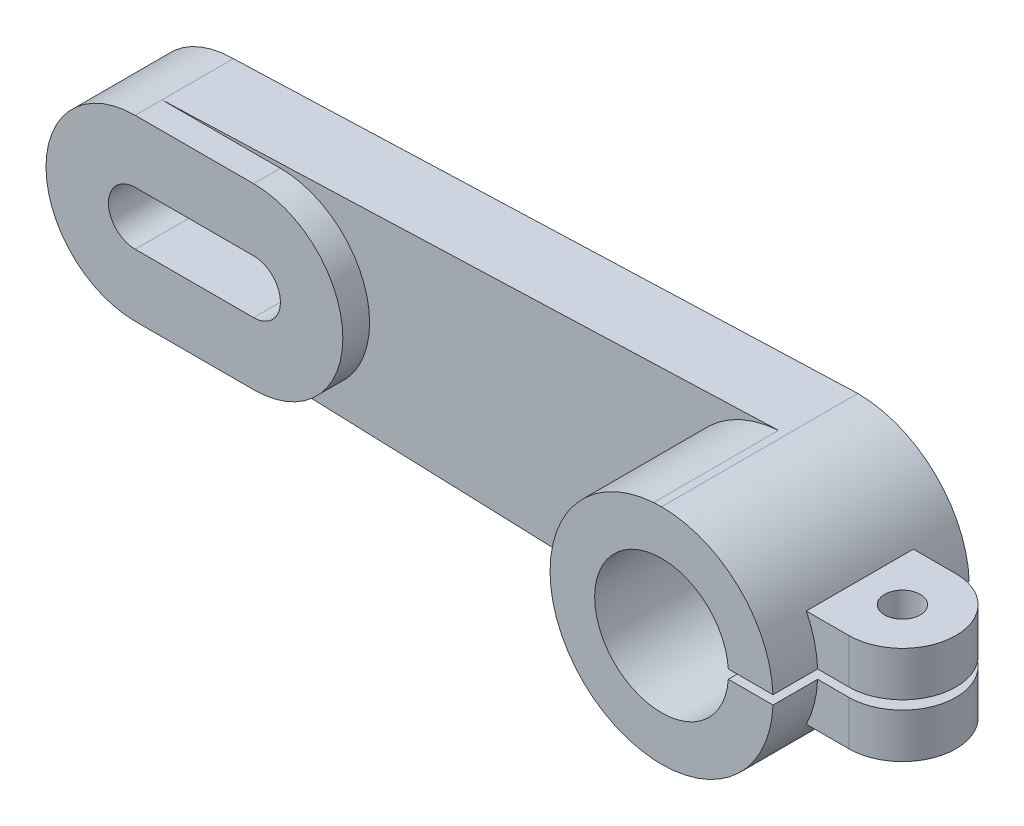
SolidWorks part; units mm, degrees
ref_plane "Přední rovina" through (0, 0, 0) normal (0, 0, 1) x (1, 0, 0)
ref_plane "Horní rovina" through (0, 0, 0) normal (0, 1, 0) x (1, 0, 0)
ref_plane "Pravá rovina" through (0, 0, 0) normal (1, 0, 0) x (0, 0, -1)
sketch "Skica2" plane through (0, 0, 0) normal (0, 0, 1) x (1, 0, 0)
  line L0 (0, 0) -> (140, 0) construction
  line L1 (0, 0) -> (26.5473, 0) construction
  line L2 (0, 6) -> (26.5473, 6)
  line L3 (0, -6) -> (26.5473, -6)
  line L4 (0, 0) -> (26.5473, 0) construction
  line L5 (0, 20) -> (26.5473, 20)
  line L6 (0, -20) -> (26.5473, -20)
  line L7 (0, 20) -> (140, 25)
  line L8 (0, -20) -> (140, -25)
  arc A0 (0, 6) -> (0, -6) centre (0, 0) ccw
  arc A1 (26.5473, -6) -> (26.5473, 6) centre (26.5473, 0) ccw
  arc A2 (0, 20) -> (0, -20) centre (0, 0) ccw
  arc A3 (26.5473, -20) -> (26.5473, 20) centre (26.5473, 0) ccw
  circle A4 centre (140, 0) radius 15
  circle A5 centre (140, 0) radius 25
  point P3 (13.2737, 0)
  point P9 (13.2737, 0)
  point P20 (0, 20)
  point P21 (140, 25)
  point P22 (0, 0)
  point P25 (0, 0)
  point P26 (0, 0)
  point P27 (0, 0)
  point P28 (140, -25)
  dimension "D3" = 50
  dimension "D4" = 30
  dimension "D1" = 6
  dimension "D2" = 20
  dimension "D5" = 140
extrude "Přidat vysunutím1" add sketch "Skica2" along normal blind 16 contours L6 A3 L5 A2 A1 L3 A0 L2 | A5 L7 L5 A3 L6 L8 | L7 A5 L8 A4 region at (81.0903, 0, 0) region at (13.2737, 19.2236, 0) region at (139.1335, 24.2615, 0)
extrude "Přidat vysunutím2" add sketch "Skica2<3>" along normal blind 22 contours L6 A3 L5 A2 A1 L3 A0 L2 region at (13.2737, 19.2236, 0)
sketch "Skica2<3>" plane through (0, 0, 0) normal (0, 0, 1) x (1, 0, 0) same geometry as "Skica2"
extrude "Přidat vysunutím3" add sketch "Skica2<4>" along normal blind 44 contours L7 A5 L8 A4 region at (139.1335, 24.2615, 0)
sketch "Skica2<4>" plane through (0, 0, 0) normal (0, 0, 1) x (1, 0, 0) same geometry as "Skica2"
sketch "Skica3" plane through (0, 0, 0) normal (0, 1, 0) x (1, 0, 0)
  line L0 (172, -10) -> (156.5202, -10)
  line L1 (172, -34) -> (156.5202, -34)
  line L2 (156.5202, -34) -> (156.5202, -10)
  line L3 (165, 0) -> (140, 0) construction
  line L4 (140, -44) -> (140, 0) construction
  circle A0 centre (172, -22) radius 4
  arc A1 (172, -34) -> (172, -10) centre (172, -22) ccw
  point P6 (156.5202, -10.7613)
  dimension "D1" = 24
  dimension "D2" = 8
  dimension "D3" = 22
  dimension "D4" = 32
extrude "Přidat vysunutím4" add sketch "Skica3" along normal mid plane 22
sketch "Skica4" plane through (0, 0, 44) normal (0, 0, 1) x (1, 0, 0)
  line L0 (140, 0) -> (190, 0) construction
  line L2 (140, 1) -> (190, 1)
  line L3 (140, 1) -> (140, -1)
  line L4 (140, -1) -> (190, -1)
  line L5 (190, 1) -> (190, -1)
  line L6 (140, 1) -> (190, -1) construction
  line L7 (140, -1) -> (190, 1) construction
  point P6 (165, 0)
  dimension "D1" = 2
  dimension "D2" = 50
extrude "Odebrat vysunutím1" cut sketch "Skica4" against normal through all
